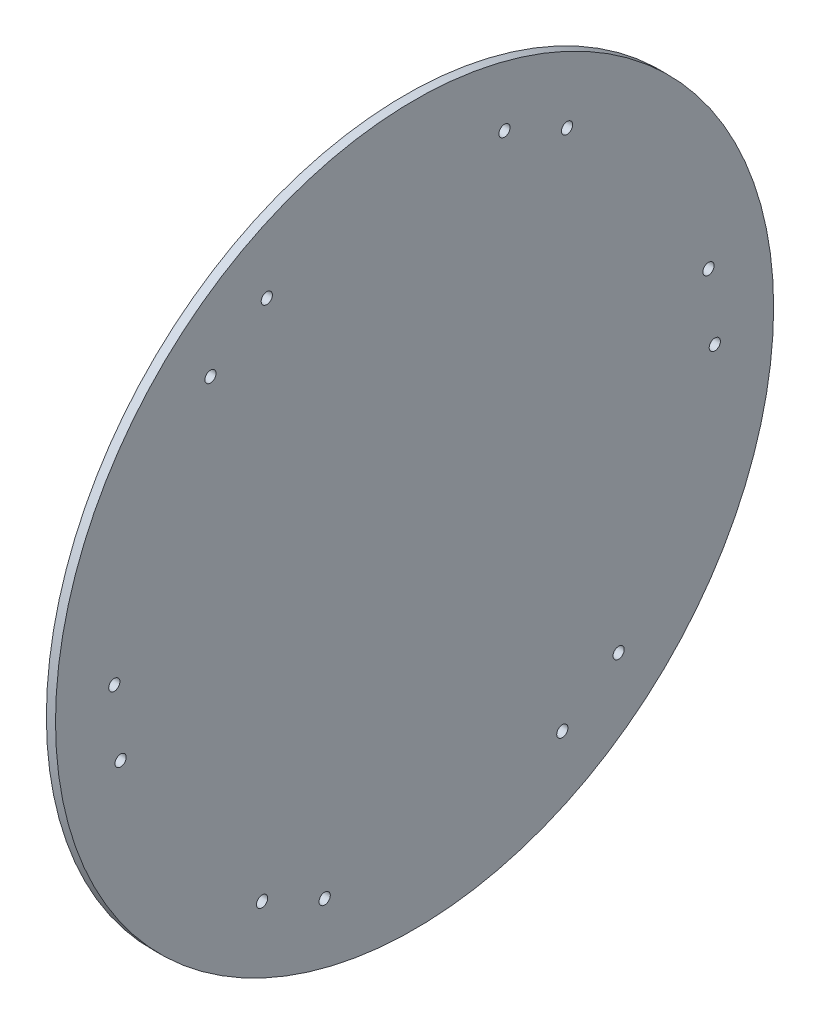
SolidWorks part; units mm, degrees
material "Oak"
ref_plane "Front Plane" through (0, 0, 0) normal (0, 0, 1) x (1, 0, 0)
ref_plane "Top Plane" through (0, 0, 0) normal (0, 1, 0) x (1, 0, 0)
ref_plane "Right Plane" through (0, 0, 0) normal (1, 0, 0) x (0, 0, -1)
sketch "Sketch2" plane through (0, 0, 0) normal (1, 0, 0) x (0, 0, -1)
  circle A0 centre (0, 0) radius 125
  dimension "D1" = 250
extrude "Boss-Extrude1" add sketch "Sketch2" along normal blind 3.18
sketch "Sketch3" plane through (0, 0, 0) normal (-1, 0, 0) x (0, 0, 1)
  circle A5 centre (104.5235, 0.9499) radius 1.95
  circle A12 centre (102.3318, -22.9498) radius 1.95
  circle A13 centre (31.2908, -100.0969) radius 1.95
  circle A14 centre (53.0844, -90.045) radius 1.95
  circle A15 centre (-51.4391, -90.9949) radius 1.95
  circle A16 centre (-71.041, -77.147) radius 1.95
  circle A17 centre (-102.3318, 22.9498) radius 1.95
  circle A18 centre (-104.5235, -0.9499) radius 1.95
  circle A19 centre (-53.0844, 90.045) radius 1.95
  circle A20 centre (-31.2908, 100.0969) radius 1.95
  circle A21 centre (51.4391, 90.9949) radius 1.95
  circle A22 centre (71.041, 77.147) radius 1.95
  dimension "D1" = 3.9
extrude "Cut-Extrude1" cut sketch "Sketch3" against normal through all
sketch "Sketch4" plane through (3.18, 0, 0) normal (1, 0, 0) x (0, 0, -1)
  line L0 (72.2937, 101.9736) -> (-72.2937, -101.9736) construction
  circle A0 centre (0, 0) radius 125 construction
